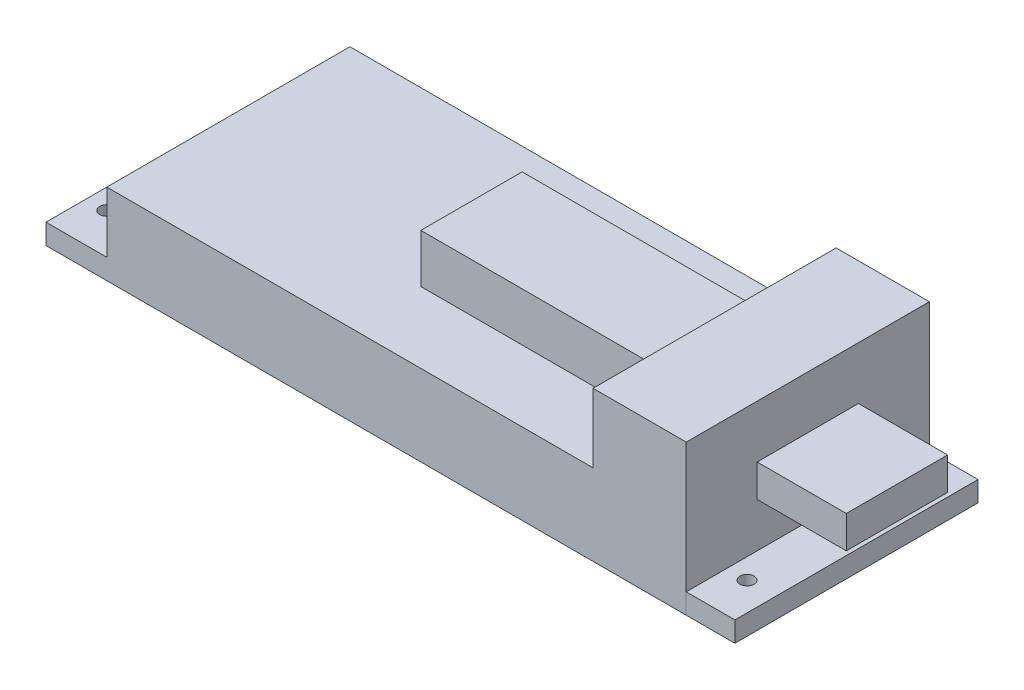
SolidWorks part; units mm, degrees
ref_plane "Front Plane" through (0, 0, 0) normal (0, 0, 1) x (1, 0, 0)
ref_plane "Top Plane" through (0, 0, 0) normal (0, 1, 0) x (1, 0, 0)
ref_plane "Right Plane" through (0, 0, 0) normal (1, 0, 0) x (0, 0, -1)
sketch "Sketch1" plane through (0, 0, 0) normal (0, 1, 0) x (1, 0, 0)
  line L0 (-55, 0) -> (55, 0) construction
  line L1 (-85, -30) -> (85, -30)
  line L2 (-85, -30) -> (-85, 30)
  line L3 (-85, 30) -> (85, 30)
  line L4 (85, -30) -> (85, 30)
  line L5 (-85, -30) -> (85, 30) construction
  line L6 (-85, 30) -> (85, -30) construction
  line L7 (-70, 30) -> (-70, -30)
  line L8 (73, 12.5) -> (95, 12.5)
  line L9 (95, 12.5) -> (95, -12.5)
  line L10 (95, -12.5) -> (73, -12.5)
  line L11 (50, 30) -> (50, -30)
  line L12 (50, 12.5) -> (-10, 12.5)
  line L13 (-10, 12.5) -> (-10, -12.5)
  line L14 (-10, -12.5) -> (50, -12.5)
  line L15 (73, -30) -> (73, 30)
  circle A0 centre (-80, 20) radius 1.75
  circle A1 centre (-80, -20) radius 1.75
  circle A2 centre (78, 20) radius 1.75
  circle A3 centre (78, -20) radius 1.75
  point P0 (0, 0)
  point P18 (85, 0)
  point P21 (95, 0)
  point P28 (-10, 0)
  point P31 (50, 0)
  point P34 (85, -12.5)
  point P35 (73, 12.5)
  point P36 (73, -12.5)
  dimension "D3" = 3.5
  dimension "D1" = 170
  dimension "D2" = 60
  dimension "D4" = 40
  dimension "D5" = 5
  dimension "D6" = 15
  dimension "D7" = 7
  dimension "D8" = 25
  dimension "D9" = 22
  dimension "D10" = 35
  dimension "D11" = 60
  dimension "D12" = 12
extrude "Boss-Extrude1" add sketch "Sketch1" along normal blind 5 contours L7 L3 L2 L1 A0 A1 | L15 L1 L4 L10 A3 | L15 L10 L4 L8 | L15 L8 L4 L3 A2 region at (-77.4454, 0, 0) region at (73.2122, 0, 21.25) region at (79, 0, 0) region at (79, 0, -29.7878)
extrude "Boss-Extrude2" add sketch "Sketch1<3>" along normal blind 20 contours L14 L13 L12 L11 L3 L7 L1 region at (-17.8947, 0, 0)
sketch "Sketch1<3>" plane through (0, 0, 0) normal (0, 1, 0) x (1, 0, 0) same geometry as "Sketch1"
extrude "Boss-Extrude3" add sketch "Sketch1<4>" along normal blind 32 contours L13 L14 L11 L12 region at (20, 0, 0)
sketch "Sketch1<4>" plane through (0, 0, 0) normal (0, 1, 0) x (1, 0, 0) same geometry as "Sketch1"
extrude "Boss-Extrude4" add sketch "Sketch1<5>" along normal blind 37 contours L3 L11 L1 L4 A3 A2 region at (61.5, 0, 0)
sketch "Sketch1<5>" plane through (0, 0, 0) normal (0, 1, 0) x (1, 0, 0) same geometry as "Sketch1"
extrude "Boss-Extrude5" add sketch "Sketch1<6>" along normal blind 8 from offset 16 contours L10 L9 L8 L4 | L15 L10 L4 L8 region at (79, 0, 0) region at (90, 0, 0)
sketch "Sketch1<6>" plane through (0, 0, 0) normal (0, 1, 0) x (1, 0, 0) same geometry as "Sketch1"
